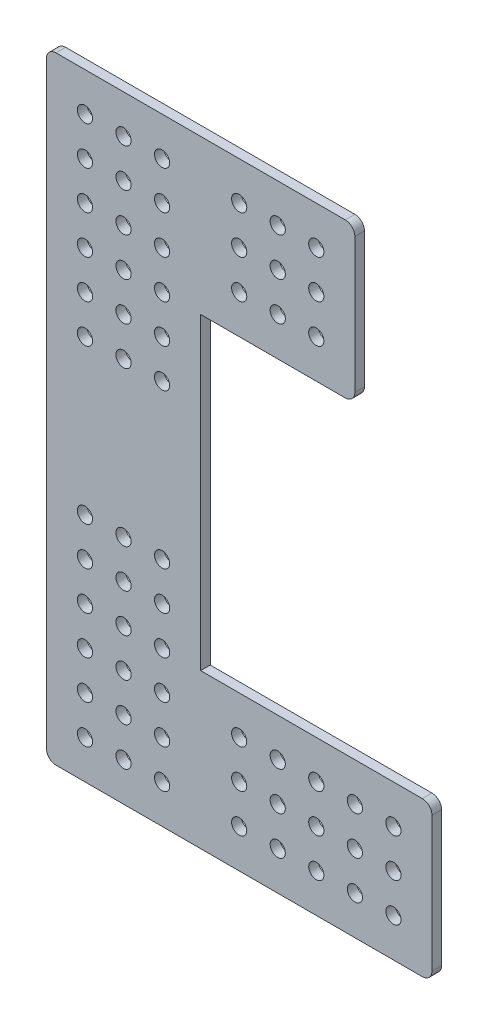
SolidWorks part; units mm, degrees
ref_plane "Front Plane" through (0, 0, 0) normal (0, 0, 1) x (1, 0, 0)
ref_plane "Top Plane" through (0, 0, 0) normal (0, 1, 0) x (1, 0, 0)
ref_plane "Right Plane" through (0, 0, 0) normal (1, 0, 0) x (0, 0, -1)
sketch "Sketch1" plane through (0, 0, 0) normal (0, 0, 1) x (1, 0, 0)
  line L0 (23.16, 167.0479) -> (26.335, 167.0479)
  line L1 (-24.465, 14.6479) -> (99.36, 14.6479)
  line L2 (-24.465, 14.6479) -> (-24.465, -32.9771)
  line L3 (-21.29, -36.1521) -> (99.36, -36.1521)
  line L4 (102.535, 11.4729) -> (102.535, -32.9771)
  line L5 (-21.29, 167.0479) -> (23.16, 167.0479)
  line L6 (-24.465, 163.8729) -> (-24.465, 14.6479)
  line L7 (-24.465, 14.6479) -> (26.335, 14.6479)
  line L8 (26.335, 163.8729) -> (26.335, 14.6479)
  line L9 (26.335, 167.0479) -> (26.335, 163.8729)
  arc A0 (-24.465, -32.9771) -> (-21.29, -36.1521) centre (-21.29, -32.9771) ccw
  arc A1 (99.36, -36.1521) -> (102.535, -32.9771) centre (99.36, -32.9771) ccw
  arc A2 (99.36, 14.6479) -> (102.535, 11.4729) centre (99.36, 11.4729) cw
  arc A4 (-21.29, 167.0479) -> (-24.465, 163.8729) centre (-21.29, 163.8729) ccw
  point P10 (-24.465, -36.1521)
  point P13 (102.535, -36.1521)
  point P16 (102.535, 14.6479)
  point P19 (26.335, 167.0479)
  point P22 (-24.465, 167.0479)
  dimension "D5" = 3.175
  dimension "D1" = 50.8
  dimension "D2" = 50.8
  dimension "D3" = 127
  dimension "D4" = 152.4
extrude "Boss-Extrude1" add sketch "Sketch1" along normal blind 3.175 contours L8 L5 L6 L1 | L4 L1 L2 L3 region at (0.9419, 90.8268, 0) region at (39.0139, -10.7439, 0)
sketch "Sketch2" plane through (0, 0, 3.175) normal (0, 0, 1) x (1, 0, 0)
  line L0 (-24.465, 163.8729) -> (-24.465, -32.9771) construction
  line L1 (-21.29, 167.0479) -> (26.335, 167.0479) construction
  line L2 (102.535, 11.4729) -> (102.535, -32.9771) construction
  line L3 (-21.29, -36.1521) -> (99.36, -36.1521) construction
  circle A0 centre (-11.765, 154.3479) radius 2.5
  circle A1 centre (89.835, -23.4521) radius 2.5
  circle A2 centre (0.935, 154.3479) radius 2.5
  circle A3 centre (13.635, 154.3479) radius 2.5
  circle A4 centre (0.935, 141.6479) radius 2.5
  circle A5 centre (13.635, 141.6479) radius 2.5
  circle A6 centre (0.935, 128.9479) radius 2.5
  circle A7 centre (13.635, 128.9479) radius 2.5
  circle A8 centre (0.935, 116.2479) radius 2.5
  circle A9 centre (13.635, 116.2479) radius 2.5
  circle A10 centre (0.935, 103.5479) radius 2.5
  circle A11 centre (13.635, 103.5479) radius 2.5
  circle A12 centre (0.935, 90.8479) radius 2.5
  circle A13 centre (13.635, 90.8479) radius 2.5
  circle A20 centre (-11.765, 141.6479) radius 2.5
  circle A21 centre (-11.765, 128.9479) radius 2.5
  circle A22 centre (-11.765, 116.2479) radius 2.5
  circle A23 centre (-11.765, 103.5479) radius 2.5
  circle A24 centre (-11.765, 90.8479) radius 2.5
  circle A28 centre (77.135, -23.4521) radius 2.5
  circle A29 centre (64.435, -23.4521) radius 2.5
  circle A30 centre (51.735, -23.4521) radius 2.5
  circle A31 centre (39.035, -23.4521) radius 2.5
  circle A33 centre (77.135, -10.7521) radius 2.5
  circle A34 centre (64.435, -10.7521) radius 2.5
  circle A35 centre (51.735, -10.7521) radius 2.5
  circle A36 centre (39.035, -10.7521) radius 2.5
  circle A38 centre (77.135, 1.9479) radius 2.5
  circle A39 centre (64.435, 1.9479) radius 2.5
  circle A40 centre (51.735, 1.9479) radius 2.5
  circle A41 centre (39.035, 1.9479) radius 2.5
  circle A43 centre (89.835, -10.7521) radius 2.5
  circle A44 centre (89.835, 1.9479) radius 2.5
  circle A45 centre (-11.765, 40.0479) radius 2.5
  circle A46 centre (0.935, 40.0479) radius 2.5
  circle A47 centre (13.635, 40.0479) radius 2.5
  circle A48 centre (-11.765, 27.3479) radius 2.5
  circle A49 centre (0.935, 27.3479) radius 2.5
  circle A50 centre (13.635, 27.3479) radius 2.5
  circle A51 centre (-11.765, 14.6479) radius 2.5
  circle A52 centre (0.935, 14.6479) radius 2.5
  circle A53 centre (13.635, 14.6479) radius 2.5
  circle A54 centre (-11.765, 1.9479) radius 2.5
  circle A55 centre (0.935, 1.9479) radius 2.5
  circle A56 centre (13.635, 1.9479) radius 2.5
  circle A57 centre (-11.765, -10.7521) radius 2.5
  circle A58 centre (0.935, -10.7521) radius 2.5
  circle A59 centre (13.635, -10.7521) radius 2.5
  circle A60 centre (-11.765, -23.4521) radius 2.5
  circle A61 centre (0.935, -23.4521) radius 2.5
  circle A62 centre (13.635, -23.4521) radius 2.5
  circle A63 centre (26.335, -23.4521) radius 2.5 [skipped]
  circle A64 centre (26.335, -10.7521) radius 2.5 [skipped]
  circle A65 centre (26.335, 1.9479) radius 2.5 [skipped]
  circle A66 centre (0.935, 78.1479) radius 2.5 [skipped]
  circle A67 centre (13.635, 78.1479) radius 2.5 [skipped]
  circle A68 centre (0.935, 65.4479) radius 2.5 [skipped]
  circle A69 centre (13.635, 65.4479) radius 2.5 [skipped]
  circle A70 centre (0.935, 52.7479) radius 2.5 [skipped]
  circle A71 centre (13.635, 52.7479) radius 2.5 [skipped]
  circle A72 centre (-11.765, 78.1479) radius 2.5 [skipped]
  circle A73 centre (-11.765, 65.4479) radius 2.5 [skipped]
  circle A74 centre (-11.765, 52.7479) radius 2.5 [skipped]
  dimension "D1" = 5
  dimension "D4" = 5
  dimension "D2" = 12.7
  dimension "D3" = 12.7
  dimension "D5" = 12.7
  dimension "D6" = 12.7
  dimension "D7" = 3
  dimension "D9" = 15
  dimension "D8" = 6
extrude "Cut-Extrude1" cut sketch "Sketch2" against normal through all
sketch "Sketch3" plane through (0, 0, 3.175) normal (0, 0, 1) x (1, 0, 0)
  line L0 (26.335, 167.0479) -> (26.335, 14.6479) construction
  line L1 (73.96, 167.0479) -> (26.335, 167.0479)
  line L2 (77.135, 163.8729) -> (77.135, 119.4229)
  line L3 (73.96, 116.2479) -> (26.335, 116.2479)
  line L4 (26.335, 167.0479) -> (26.335, 116.2479)
  line L5 (-21.29, 167.0479) -> (26.335, 167.0479) construction
  arc A0 (77.135, 119.4229) -> (73.96, 116.2479) centre (73.96, 119.4229) cw
  arc A1 (73.96, 167.0479) -> (77.135, 163.8729) centre (73.96, 163.8729) cw
  point P10 (77.135, 116.2479)
  point P13 (77.135, 167.0479)
  dimension "D3" = 3.175
  dimension "D1" = 50.8
  dimension "D2" = 50.8
extrude "Boss-Extrude2" add sketch "Sketch3" against normal up to surface (3.175 mm away) up to face at (66.935, -10.7521, 0)
sketch "Sketch4" plane through (0, 0, 3.175) normal (0, 0, 1) x (1, 0, 0)
  line L0 (77.135, 119.4229) -> (77.135, 163.8729) construction
  line L1 (-21.29, 167.0479) -> (73.96, 167.0479) construction
  circle A0 centre (64.435, 154.3479) radius 2.505
  circle A1 centre (51.735, 154.3479) radius 2.505
  circle A2 centre (39.035, 154.3479) radius 2.505
  circle A4 centre (51.735, 141.6479) radius 2.505
  circle A5 centre (39.035, 141.6479) radius 2.505
  circle A7 centre (51.735, 128.9479) radius 2.505
  circle A8 centre (39.035, 128.9479) radius 2.505
  circle A10 centre (64.435, 141.6479) radius 2.505
  circle A11 centre (64.435, 128.9479) radius 2.505
  circle A12 centre (26.335, 154.3479) radius 2.505 [skipped]
  circle A13 centre (26.335, 141.6479) radius 2.505 [skipped]
  circle A14 centre (26.335, 128.9479) radius 2.505 [skipped]
  dimension "D1" = 5.01
  dimension "D2" = 12.7
  dimension "D3" = 12.7
  dimension "D4" = 4
extrude "Cut-Extrude2" cut sketch "Sketch4" against normal through all
